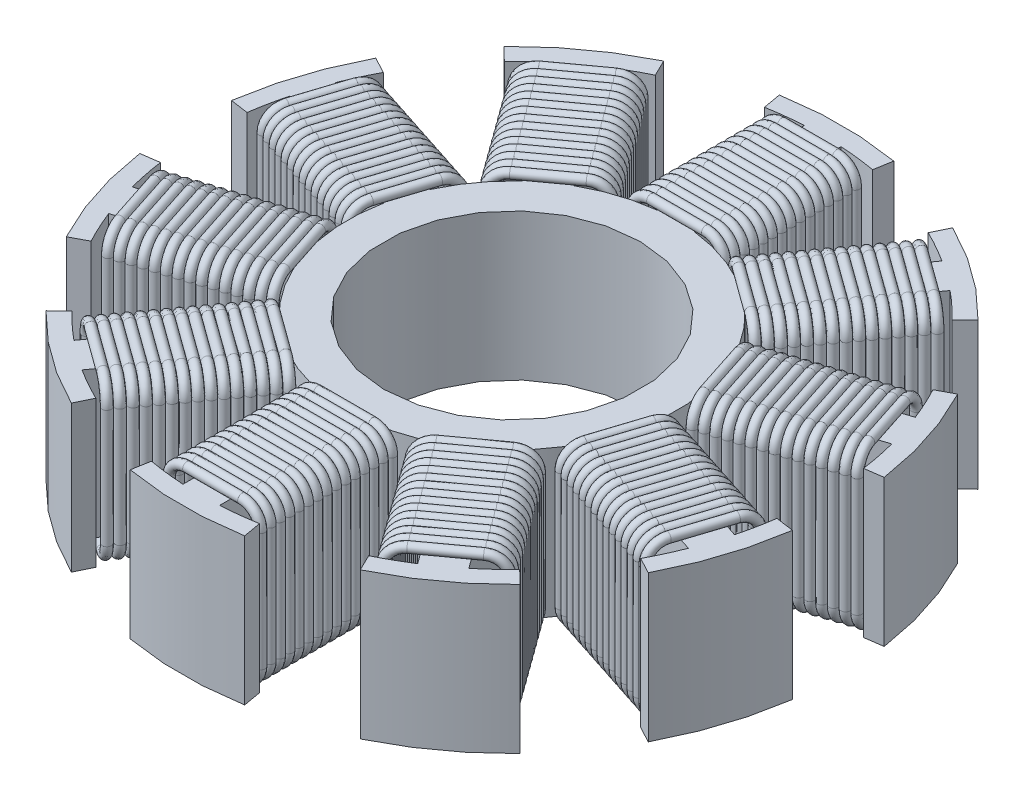
SolidWorks part; units mm, degrees
ref_plane "Front Plane" through (0, 0, 0) normal (0, 0, 1) x (1, 0, 0)
ref_plane "Top Plane" through (0, 0, 0) normal (0, 1, 0) x (1, 0, 0)
ref_plane "Right Plane" through (0, 0, 0) normal (1, 0, 0) x (0, 0, -1)
sketch "Sketch1" plane through (0, 0, 0) normal (0, 1, 0) x (1, 0, 0)
  line L0 (0, 14.991) -> (0, 0) construction
  line L1 (-3.1257, 17.7265) -> (-2.952, 16.7417)
  line L2 (2.952, 16.7417) -> (3.1257, 17.7265)
  line L3 (-1, 16.9706) -> (-1, 8.9443)
  line L4 (1, 16.9706) -> (1, 8.9443)
  circle A0 centre (0, 0) radius 9
  circle A1 centre (0, 0) radius 7
  arc A2 (-3.1257, 17.7265) -> (3.1257, 17.7265) centre (0, 0) cw
  arc A3 (-2.952, 16.7417) -> (-1, 16.9706) centre (0, 0) cw
  arc A4 (1, 16.9706) -> (2.952, 16.7417) centre (0, 0) cw
  arc A5 (-2.952, 16.7417) -> (2.952, 16.7417) centre (0, 0) cw construction
  dimension "D1" = 14
  dimension "D2" = 2
  dimension "D3" = 18
  dimension "D5" = 2
  dimension "D6" = 20
  dimension "D7" = 0.9848
  dimension "D4" = 1
extrude "Boss-Extrude1" add sketch "Sketch1" along normal blind 8 contours A0 A1 region at (0, 0, -8.7454)
extrude "Boss-Extrude2" add sketch "Sketch1<3>" along normal blind 8 contours L4 A4 L2 A2 L1 A3 L3 A0 region at (0, 0, -14.2089)
sketch "Sketch1<3>" plane through (0, 0, 0) normal (0, 1, 0) x (1, 0, 0) same geometry as "Sketch1"
ref_plane "Plane1" through (0, 0, -9.1) normal (0, 0, 1) x (1, 0, 0)
sketch "Sketch2" plane through (0, 0, -9.1) normal (0, 0, 1) x (1, 0, 0)
  line L0 (0, 8) -> (0, 0) construction
  line L1 (9, 8) -> (-9, 8) construction
  line L2 (-1.5, 8.225) -> (1.5, 8.225)
  line L3 (-2.5, 7.225) -> (-2.5, 0.775)
  line L4 (-1.5, -0.225) -> (1.5, -0.225)
  line L5 (2.5, 7.225) -> (2.5, 0.775)
  line L6 (-2.5, 8.225) -> (2.5, -0.225) construction
  line L7 (-2.5, -0.225) -> (2.5, 8.225) construction
  line L8 (-9, 0) -> (9, 0) construction
  arc A0 (1.5, -0.225) -> (2.5, 0.775) centre (1.5, 0.775) ccw
  arc A1 (-2.5, 0.775) -> (-1.5, -0.225) centre (-1.5, 0.775) ccw
  arc A2 (1.5, 8.225) -> (2.5, 7.225) centre (1.5, 7.225) cw
  arc A3 (-1.5, 8.225) -> (-2.5, 7.225) centre (-1.5, 7.225) ccw
  point P3 (0, 4)
  dimension "D3" = 1
  dimension "D1" = 5
  dimension "D2" = 8.45
sketch "Sketch3" plane through (0, 0, 0) normal (1, 0, 0) x (0, 0, -1)
  line L0 (9.1, -0.225) -> (9.1, 8.225) construction
  circle A0 centre (9.1, 8.225) radius 0.25
  dimension "D1" = 0.5
sweep "Sweep1" add profiles "Sketch3" path "Sketch2"
pattern_linear "LPattern1" count 15 spacing 0.51 along (0, 0, -1) of "Sweep1"
pattern_circular "CirPattern1" count 10 over 360 of "Boss-Extrude2", "Sweep1", "LPattern1"
